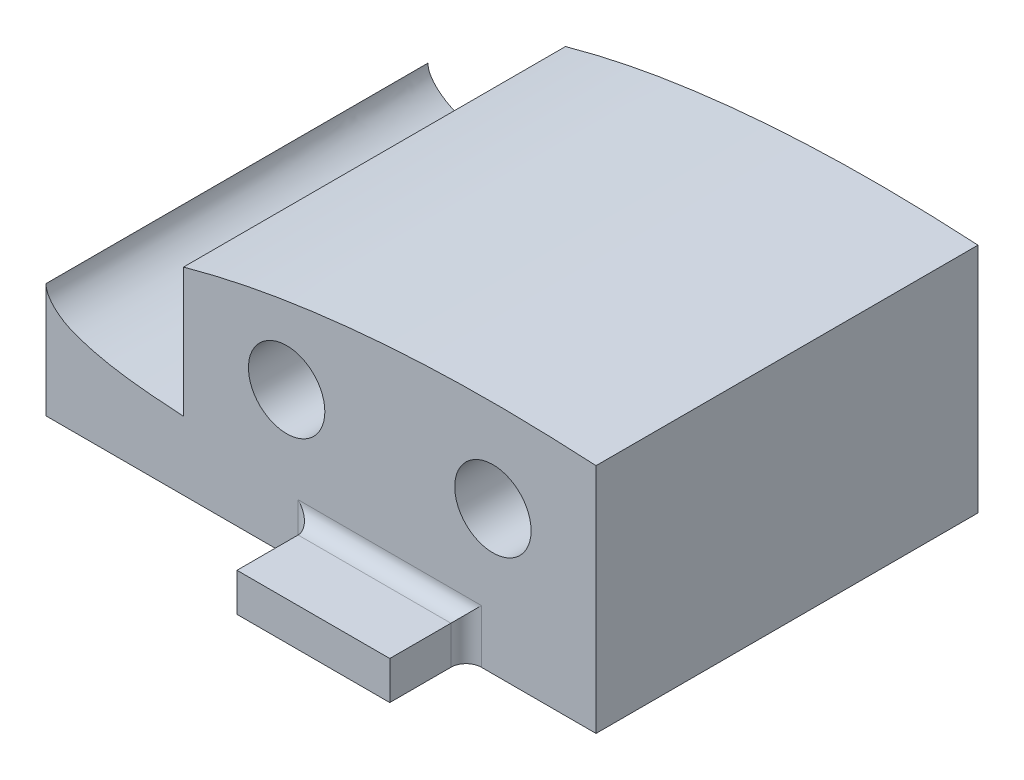
SolidWorks part; units mm, degrees
ref_plane "Front Plane" through (0, 0, 0) normal (0, 0, 1) x (1, 0, 0)
ref_plane "Top Plane" through (0, 0, 0) normal (0, 1, 0) x (1, 0, 0)
ref_plane "Right Plane" through (0, 0, 0) normal (1, 0, 0) x (0, 0, -1)
curve "Curve1"
  spline degree 3 poles (25.4, 0.033, 0) (24.9771, 0.1481, 0) (24.1334, 0.3778, 0) (22.4431, 0.7955, 0) (20.3293, 1.2569, 0) (17.7869, 1.7118, 0) (15.2464, 2.0846, 0) (12.7045, 2.3505, 0) (10.1628, 2.5164, 0) (8.041, 2.5181, 0) (6.3469, 2.4009, 0) (5.0745, 2.2465, 0) (3.7995, 2.0188, 0) (2.7428, 1.745, 0) (1.8961, 1.4685, 0) (1.2577, 1.2074, 0) (0.7129, 0.9251, 0) (0.2401, 0.5874, 0) (-0.1715, 0.0442, 0) (0.2727, -0.3711, 0) (0.7261, -0.5342, 0) (1.266, -0.6443, 0) (1.9036, -0.7002, 0) (2.7513, -0.7398, 0) (3.8103, -0.7368, 0) (5.0806, -0.7013, 0) (6.3499, -0.6336, 0) (8.0433, -0.5544, 0) (10.1596, -0.4528, 0) (12.7001, -0.3574, 0) (15.2397, -0.2514, 0) (17.7796, -0.1611, 0) (20.3198, -0.0947, 0) (22.4366, -0.061, 0) (24.13, -0.0388, 0) (24.9767, -0.035, 0) (25.4, -0.033, 0) knots 0 0 0 0 0.025305 0.050488 0.10052 0.150191 0.199587 0.24874 0.297716 0.346601 0.371103 0.395726 0.42057 0.445825 0.458702 0.47192 0.485786 0.493461 0.506863 0.516148 0.522766 0.535269 0.547551 0.559786 0.584229 0.608681 0.633151 0.657622 0.706558 0.755482 0.804406 0.85332 0.902221 0.951113 0.975557 1 1 1 1
sketch "Original NACA 4412" plane through (0, 0, 0) normal (0, 0, 1) x (1, 0, 0)
  line L0 (25.4, 0.033) -> (25.4, -0.033)
  spline S0 degree 3 poles (623.3011, 1907.6527) (79.6214, -43.1606) (55.117, -7.2775) (22.4431, 0.7955) (20.3293, 1.2569) (17.7869, 1.7118) (15.2464, 2.0846) (12.7045, 2.3505) (10.1628, 2.5164) (8.041, 2.5181) (6.3469, 2.4009) (5.0745, 2.2465) (3.7995, 2.0188) (2.7428, 1.745) (1.8961, 1.4685) (1.2577, 1.2074) (0.7129, 0.9251) (0.2401, 0.5874) (-0.1715, 0.0442) (0.2727, -0.3711) (0.7261, -0.5342) (1.266, -0.6443) (1.9036, -0.7002) (2.7513, -0.7398) (3.8103, -0.7368) (5.0806, -0.7013) (6.3499, -0.6336) (8.0433, -0.5544) (10.1596, -0.4528) (12.7001, -0.3574) (15.2397, -0.2514) (17.7796, -0.1611) (20.3198, -0.0947) (22.4366, -0.061) (67.8901, 0.5348) (112.6717, -18.929) (139.2928, 1995.2022) knots -1.842584 -1.842584 -1.842584 -1.842584 0.025305 0.050488 0.10052 0.150191 0.199587 0.24874 0.297716 0.346601 0.371103 0.395726 0.42057 0.445825 0.458702 0.47192 0.485786 0.493461 0.506863 0.516148 0.522766 0.535269 0.547551 0.559786 0.584229 0.608681 0.633151 0.657622 0.706558 0.755482 0.804406 0.85332 0.902221 0.951113 0.975557 3.526814 3.526814 3.526814 3.526814 only from (25.4, 0.033) to (25.4, -0.033) construction
  spline S1 degree 3 poles (25.4, 0.033) (24.9771, 0.1481) (24.1334, 0.3778) (22.4431, 0.7955) (20.3293, 1.2569) (17.7869, 1.7118) (15.2464, 2.0846) (12.7045, 2.3505) (10.1628, 2.5164) (8.041, 2.5181) (6.3469, 2.4009) (5.0745, 2.2465) (3.7995, 2.0188) (2.7428, 1.745) (1.8961, 1.4685) (1.2577, 1.2074) (0.7129, 0.9251) (0.2401, 0.5874) (-0.1715, 0.0442) (0.2727, -0.3711) (0.7261, -0.5342) (1.266, -0.6443) (1.9036, -0.7002) (2.7513, -0.7398) (3.8103, -0.7368) (5.0806, -0.7013) (6.3499, -0.6336) (8.0433, -0.5544) (10.1596, -0.4528) (12.7001, -0.3574) (15.2397, -0.2514) (17.7796, -0.1611) (20.3198, -0.0947) (22.4366, -0.061) (24.13, -0.0388) (24.9767, -0.035) (25.4, -0.033) knots 0 0 0 0 0.025305 0.050488 0.10052 0.150191 0.199587 0.24874 0.297716 0.346601 0.371103 0.395726 0.42057 0.445825 0.458702 0.47192 0.485786 0.493461 0.506863 0.516148 0.522766 0.535269 0.547551 0.559786 0.584229 0.608681 0.633151 0.657622 0.706558 0.755482 0.804406 0.85332 0.902221 0.951113 0.975557 1 1 1 1
sketch "Scaled and rotated by 1.5°" plane through (0, 0, 0) normal (0, 0, 1) x (1, 0, 0)
  line L0 (228.6156, -6.2198) -> (228.6, -6.8141)
  line L1 (40.005, 17.5068) -> (40.005, -8.0377) construction
  line L2 (0, 2.8493) -> (0, 0) construction
  line L3 (40.005, 4.7346) -> (74.295, 4.7346) construction
  line L4 (74.295, 4.7346) -> (40.005, 4.7346) construction
  line L5 (228.6, -6.8141) -> (228.6, -6.2434) construction
  circle A0 centre (40.005, 4.7346) radius 4.7625
  circle A1 centre (74.295, 4.7346) radius 4.7625
  spline S1 degree 3 poles (228.6156, -6.2198) (224.8373, -5.0843) (217.299, -2.8187) (202.1877, 1.3376) (183.276, 5.9878) (160.5054, 10.6799) (137.7331, 14.6335) (114.9229, 17.6255) (92.0911, 19.717) (72.9986, 20.2321) (57.7264, 19.5766) (46.2411, 18.4872) (34.7139, 16.739) (25.1416, 14.5242) (17.4573, 12.2353) (11.6508, 10.0367) (6.6824, 7.6245) (2.3479, 4.6971) (-1.484, -0.0934) (2.416, -3.9359) (6.457, -5.51) (11.2894, -6.6275) (17.0139, -7.2813) (24.6323, -7.8374) (34.1618, -8.0602) (45.6007, -8.0396) (57.039, -7.7297) (72.295, -7.4161) (91.3623, -7.0002) (114.245, -6.7401) (137.1228, -6.385) (159.999, -6.1713) (182.8715, -6.1724) (201.9277, -6.3679) (217.1704, -6.5672) (224.7902, -6.7318) (228.6, -6.8141) knots 0 0 0 0 0.025305 0.050488 0.10052 0.150191 0.199587 0.24874 0.297716 0.346601 0.371103 0.395726 0.42057 0.445825 0.458702 0.47192 0.485786 0.493461 0.506863 0.516148 0.522766 0.535269 0.547551 0.559786 0.584229 0.608681 0.633151 0.657622 0.706558 0.755482 0.804406 0.85332 0.902221 0.951113 0.975557 1 1 1 1
  dimension "D2" = 9.525
  dimension "D1" = 40.005
  dimension "D3" = 34.29
  dimension "D5" = 228.6
  dimension "D4" = 1.5
sketch "Sketch6" plane through (0, 0, 0) normal (0, 0, 1) x (1, 0, 0)
  line L1 (40.005, 17.5068) -> (40.005, -8.0377) construction
  line L2 (0, 2.2821) -> (0, 0) construction
  line L3 (40.005, 4.7346) -> (74.295, 4.7346) construction
  line L4 (74.295, 4.7346) -> (40.005, 4.7346) construction
  line L6 (0, 0) -> (0, -19.05)
  line L7 (0, -19.05) -> (91.44, -19.05)
  line L8 (91.44, -19.05) -> (91.44, 19.5089)
  line L9 (22.86, -7.6743) -> (22.86, 13.8098)
  circle A0 centre (40.005, 4.7346) radius 6.35
  circle A1 centre (74.295, 4.7346) radius 6.35
  spline S0 degree 3 poles (0, 0) (0, -0.1787) (0.1349, -1.6884) (2.416, -3.9359) (6.457, -5.51) (11.2894, -6.6275) (17.0139, -7.2813) (20.8709, -7.5628) (22.818, -7.672) (22.86, -7.6743) knots 0.505626 0.505626 0.505626 0.505626 0.506863 0.516148 0.522766 0.535269 0.547551 0.559786 0.560056 0.560056 0.560056 0.560056
  spline S2 degree 3 poles (91.44, 19.5089) (84.0356, 19.9341) (72.792, 20.2232) (57.7264, 19.5766) (46.2411, 18.4872) (34.7139, 16.739) (26.9508, 14.9428) (23.0064, 13.8507) (22.86, 13.8098) knots 0.299041 0.299041 0.299041 0.299041 0.346601 0.371103 0.395726 0.42057 0.445825 0.446799 0.446799 0.446799 0.446799
  dimension "D1" = 40.005
  dimension "D3" = 34.29
  dimension "D2" = 12.7
  dimension "D6" = 91.44
  dimension "D7" = 22.86
  dimension "D4" = 19.05
extrude "Boss-Extrude2" add sketch "Sketch6" along normal blind 31.75 and the other way blind 31.75
sketch "Sketch7" plane through (0, -19.05, 0) normal (0, -1, 0) x (1, 0, 0)
  line L0 (0, 31.75) -> (91.44, 31.75) construction
  line L1 (44.45, 31.75) -> (69.85, 31.75)
  line L2 (44.45, 31.75) -> (44.45, 44.45)
  line L3 (44.45, 44.45) -> (69.85, 44.45)
  line L4 (69.85, 31.75) -> (69.85, 44.45)
  line L5 (57.15, 44.45) -> (57.15, 31.75) construction
  line L6 (0, 0) -> (35.4889, 0) construction
  line L7 (57.15, -44.45) -> (57.15, -31.75) construction
  line L8 (69.85, -31.75) -> (69.85, -44.45)
  line L9 (44.45, -44.45) -> (69.85, -44.45)
  line L10 (44.45, -31.75) -> (44.45, -44.45)
  line L11 (44.45, -31.75) -> (69.85, -31.75)
  circle A0 centre (57.15, 15.875) radius 3.175
  circle A1 centre (57.15, -15.875) radius 3.175
  point P6 (57.15, 44.45)
  dimension "D2" = 12.7
  dimension "D4" = 6.35
  dimension "D1" = 57.15
  dimension "D5" = 15.875
extrude "Boss-Extrude3" add sketch "Sketch7" against normal blind 6.35
fillet "Fillet2" radius 2.54 6 edges at (57.15, -12.7, 31.75) (44.45, -15.875, 31.75) (69.85, -15.875, 31.75) (57.15, -12.7, -31.75) (69.85, -15.875, -31.75) (44.45, -15.875, -31.75)
equation "\"span\"= 48"
equation "\"wing_chord\"= 9"
equation "\"fuse_len\"= 15"
equation "\"fuse_height\"= 5"
equation "\"fuse_wid\"= 5"
equation "\"foam_t\"= 0.1875"
equation "\"main_spar_len\"= 36"
equation "\"x_fuse_to_wing\"= 3"
equation "\"x_cg_from_le\"= 2.25"
equation "\"boom_len\"= 30"
equation "\"wing_angle\"= 1.5"
equation "\"boom_d\"= 0.75"
equation "\"wing_spar_d\"= 0.375"
equation "\"wing_spar_l\"= 48"
equation "\"wing_spar_spacing\"= 1.35"
equation "\"wing_mount_l\"= 2.5"
equation "\"vstab_span\"= 6.5"
equation "\"hstab_span\"= 15.25"
equation "\"tail_chord\"= 5"
equation "\"D1@Scaled and rotated by 1.5°\"= \"x_cg_from_le\" - \"wing_spar_spacing\"/2"
equation "\"D2@Scaled and rotated by 1.5°\"= \"wing_spar_d\""
equation "\"D3@Scaled and rotated by 1.5°\"=\"wing_spar_spacing\""
equation "\"D5@Scaled and rotated by 1.5°\"= \"wing_chord\""
equation "\"D3@Sketch6\"= \"wing_spar_spacing\""
equation "\"D1@Sketch6\"=\"x_cg_from_le\" - \"wing_spar_spacing\"/2"
equation "\"D6@Sketch6\"= \"wing_chord\"*0.4"
equation "\"D7@Sketch6\"= \"x_cg_from_le\"-\"wing_spar_spacing\""
equation "\"D1@Sketch7\"= \"x_cg_from_le\""
equation "\"D2@Boss-Extrude2\"= \"wing_mount_l\"/2"
equation "\"D1@Boss-Extrude2\"= \"wing_mount_l\"/2"
equation "\"wing_mount_bolt_spacing\" = \"wing_mount_l\" * 0.5"
equation "\"boom_mount_l\"= 1"
equation "\"D5@Sketch7\"= \"wing_mount_bolt_spacing\"/2"
